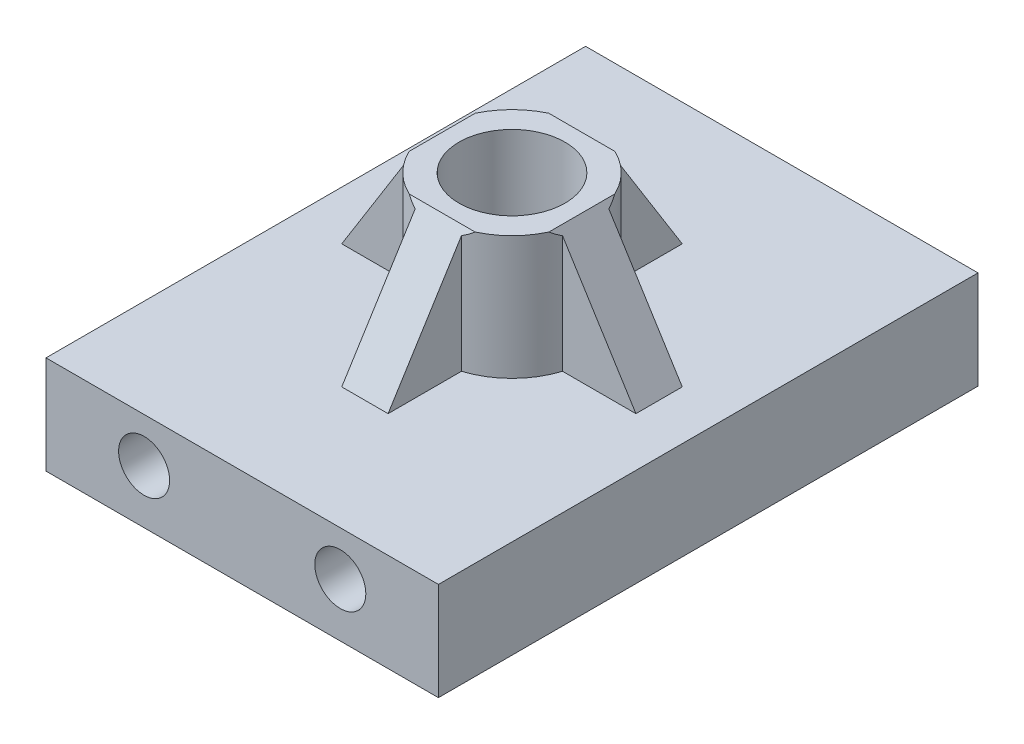
SolidWorks part; units mm, degrees
ref_plane "Front Plane" through (0, 0, 0) normal (0, 0, 1) x (1, 0, 0)
ref_plane "Top Plane" through (0, 0, 0) normal (0, 1, 0) x (1, 0, 0)
ref_plane "Right Plane" through (0, 0, 0) normal (1, 0, 0) x (0, 0, -1)
sketch "Sketch1" plane through (0, 0, 0) normal (0, 0, 1) x (1, 0, 0)
  line L1 (0, 0) -> (25.4, 0)
  line L2 (0, 0) -> (0, 6.35)
  line L3 (0, 6.35) -> (25.4, 6.35)
  line L4 (25.4, 0) -> (25.4, 6.35)
  dimension "D1" = 25.4
  dimension "D2" = 6.35
extrude "Boss-Extrude1" add sketch "Sketch1" along normal blind 34.925
sketch "Sketch2" plane through (0, 0, 34.925) normal (0, 0, 1) x (1, 0, 0)
  line L0 (0, 6.35) -> (0, 0) construction
  line L1 (25.4, 6.35) -> (0, 6.35) construction
  circle A0 centre (6.35, 3.4721) radius 1.651
  circle A1 centre (19.05, 3.4721) radius 1.651
  point P5 (0, 3.175)
  point P6 (12.7, 6.35)
  dimension "D1" = 3.302
  dimension "D2" = 12.7
  dimension "D3" = 6.35
extrude "Cut-Extrude1" cut sketch "Sketch2" against normal blind 15
ref_plane "Plane1" through (0, 0, 17.4625) normal (0, 0, 1) x (1, 0, 0)
mirror "Mirror1" about plane through (0, 0, 17.4625) normal (0, 0, 1) of "Cut-Extrude1"
sketch "Sketch3" plane through (0, 6.35, 0) normal (0, 1, 0) x (1, 0, 0)
  line L0 (25.4, 0) -> (0, 0) construction
  line L1 (0, -34.925) -> (0, 0) construction
  circle A0 centre (12.7, -17.4625) radius 3.429
  point P2 (12.7, 0)
  point P3 (0, -17.4625)
  dimension "D1" = 6.858
extrude "Cut-Extrude2" cut sketch "Sketch3" against normal through all
sketch "Sketch4" plane through (0, 6.35, 0) normal (0, 1, 0) x (1, 0, 0)
  circle A0 centre (12.7, -17.4625) radius 3.429
  circle A1 centre (12.7, -17.4625) radius 5
  circle A2 centre (12.7, -17.4625) radius 3.429 construction
  dimension "D1" = 10
extrude "Boss-Extrude2" add sketch "Sketch4" along normal blind 8
sketch "Sketch5" plane through (0, 6.35, 0) normal (0, 1, 0) x (1, 0, 0)
  line L1 (11.2, -6.6928) -> (14.2, -6.6928)
  line L2 (11.2, -6.6928) -> (11.2, -12.6928)
  line L3 (11.2, -12.6928) -> (14.2, -12.6928)
  line L4 (14.2, -6.6928) -> (14.2, -12.6928)
  circle A0 centre (12.7, -17.4625) radius 5 construction
  point P4 (12.7, -17.4625)
  point P5 (12.7, -6.6928)
  point P7 (0, 0)
  point P8 (0, 0)
  dimension "D1" = 3
  dimension "D2" = 6
extrude "Boss-Extrude3" add sketch "Sketch5" along normal up to surface (8 mm away) up to face at (12.7, 14.35, 22.4625)
chamfer "Chamfer1" distance 10 angle 32 1 edges at (12.7, 14.35, 6.6928) first distance on face at (12.7, 10.35, 6.6928)
pattern_circular "CirPattern1" count 4 over 360 about axis through (12.7, 14.35, 17.4625) along (0, -1, 0) of "Boss-Extrude3", "Chamfer1" reverse direction yes
